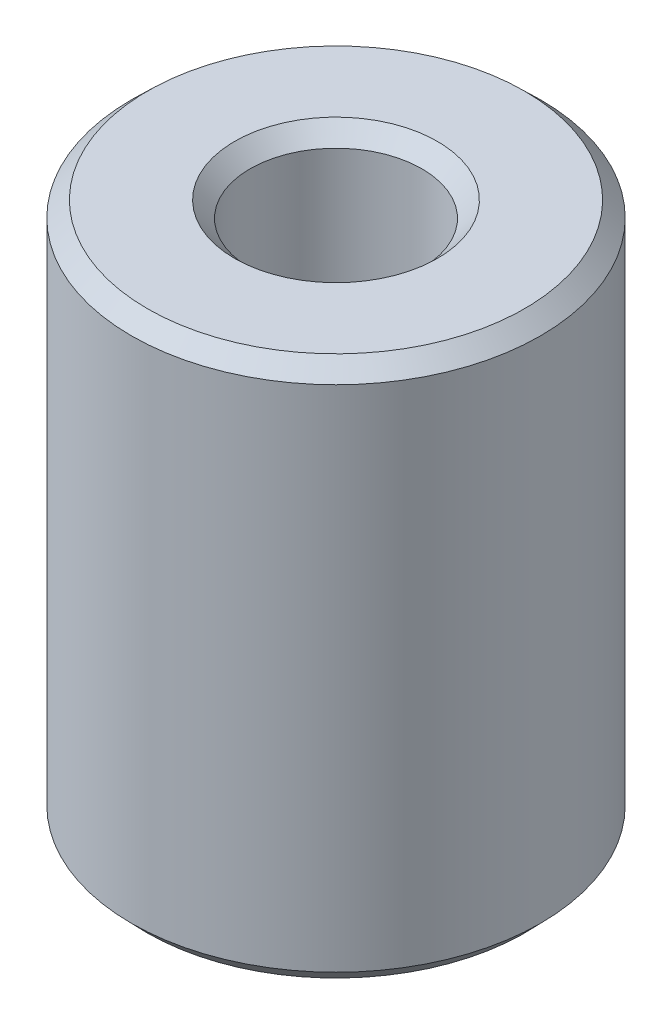
SolidWorks part; units mm, degrees
ref_plane "Front Plane" through (0, 0, 0) normal (0, 0, 1) x (1, 0, 0)
ref_plane "Top Plane" through (0, 0, 0) normal (0, 1, 0) x (1, 0, 0)
ref_plane "Right Plane" through (0, 0, 0) normal (1, 0, 0) x (0, 0, -1)
sketch "Sketch1" plane through (0, 0, 0) normal (0, 1, 0) x (1, 0, 0)
  circle A0 centre (0, 0) radius 20
  dimension "SLEEVE_OD" = 40
extrude "Boss-Extrude1" add sketch "Sketch1" along normal blind 52.833
sketch "Sketch2" plane through (0, 0, 0) normal (0, 1, 0) x (1, 0, 0)
  circle A0 centre (0, 0) radius 8.4041
  dimension "BORE_D" = 16.8081
extrude "Cut-Extrude1" cut sketch "Sketch2" along normal through all
chamfer "Chamfer1" distance 1.5143 angle 45.905 4 edges at (0, 52.833, 8.4041) (0, 0, 8.4041) (0, 0, 20) (0, 52.833, 20) first distance on face at (0, 52.833, 8.4041) first distance on face at (0, 0, 8.4041) first distance on face at (0, 52.833, 20)
